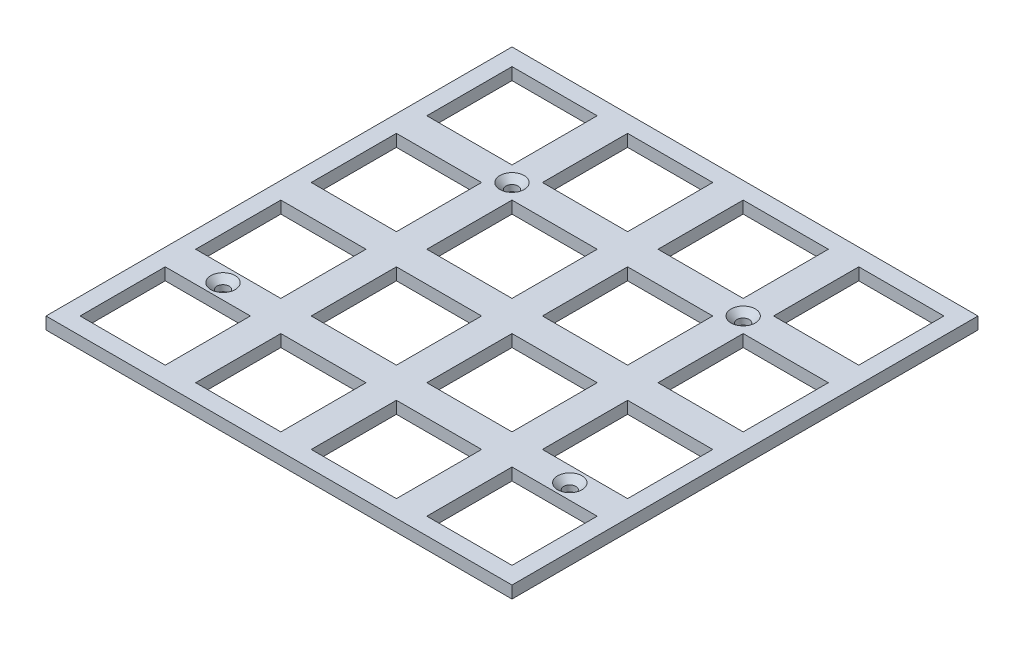
SolidWorks part; units mm, degrees
ref_plane "Front Plane" through (0, 0, 0) normal (0, 0, 1) x (1, 0, 0)
ref_plane "Top Plane" through (0, 0, 0) normal (0, 1, 0) x (1, 0, 0)
ref_plane "Right Plane" through (0, 0, 0) normal (1, 0, 0) x (0, 0, -1)
sketch "Sketch5" plane through (0, 0, 0) normal (1, 0, 0) x (0, 0, -1)
  line L0 (0, 0) -> (0, 13.4604) construction
sketch "Sketch1" plane through (0, 0, 0) normal (0, 1, 0) x (1, 0, 0)
  line L5 (-16.5, 21.5) -> (-16.5, 35.5)
  line L6 (-38.5, -38.5) -> (38.5, -38.5)
  line L11 (-38.5, -38.5) -> (-38.5, 38.5)
  line L12 (-38.5, 38.5) -> (38.5, 38.5)
  line L72 (38.5, -38.5) -> (38.5, 38.5)
  line L88 (-38.5, -38.5) -> (38.5, 38.5) construction
  line L89 (-38.5, 38.5) -> (38.5, -38.5) construction
  line L90 (-35.5, 21.5) -> (-21.5, 21.5)
  line L91 (-35.5, 21.5) -> (-35.5, 35.5)
  line L92 (-35.5, 35.5) -> (-21.5, 35.5)
  line L93 (-21.5, 21.5) -> (-21.5, 35.5)
  line L94 (-35.5, 21.5) -> (-21.5, 35.5) construction
  line L95 (-35.5, 35.5) -> (-21.5, 21.5) construction
  line L96 (-16.5, 21.5) -> (-2.5, 21.5)
  line L97 (-2.5, 21.5) -> (-2.5, 35.5)
  line L98 (-16.5, 35.5) -> (-2.5, 35.5)
  line L99 (2.5, 21.5) -> (2.5, 35.5)
  line L100 (2.5, 21.5) -> (16.5, 21.5)
  line L101 (16.5, 21.5) -> (16.5, 35.5)
  line L102 (2.5, 35.5) -> (16.5, 35.5)
  line L103 (21.5, 21.5) -> (21.5, 35.5)
  line L104 (21.5, 21.5) -> (35.5, 21.5)
  line L105 (35.5, 21.5) -> (35.5, 35.5)
  line L106 (21.5, 35.5) -> (35.5, 35.5)
  line L107 (-16.5, 2.5) -> (-16.5, 16.5)
  line L108 (-16.5, 2.5) -> (-2.5, 2.5)
  line L109 (-2.5, 2.5) -> (-2.5, 16.5)
  line L110 (-16.5, 16.5) -> (-2.5, 16.5)
  line L111 (2.5, 2.5) -> (2.5, 16.5)
  line L112 (2.5, 2.5) -> (16.5, 2.5)
  line L113 (16.5, 2.5) -> (16.5, 16.5)
  line L114 (2.5, 16.5) -> (16.5, 16.5)
  line L115 (21.5, 2.5) -> (21.5, 16.5)
  line L116 (21.5, 2.5) -> (35.5, 2.5)
  line L117 (35.5, 2.5) -> (35.5, 16.5)
  line L118 (21.5, 16.5) -> (35.5, 16.5)
  line L119 (-16.5, -16.5) -> (-16.5, -2.5)
  line L120 (-16.5, -16.5) -> (-2.5, -16.5)
  line L121 (-2.5, -16.5) -> (-2.5, -2.5)
  line L122 (-16.5, -2.5) -> (-2.5, -2.5)
  line L123 (2.5, -16.5) -> (2.5, -2.5)
  line L124 (2.5, -16.5) -> (16.5, -16.5)
  line L125 (16.5, -16.5) -> (16.5, -2.5)
  line L126 (2.5, -2.5) -> (16.5, -2.5)
  line L127 (21.5, -16.5) -> (21.5, -2.5)
  line L128 (21.5, -16.5) -> (35.5, -16.5)
  line L129 (35.5, -16.5) -> (35.5, -2.5)
  line L130 (21.5, -2.5) -> (35.5, -2.5)
  line L131 (-16.5, -35.5) -> (-16.5, -21.5)
  line L132 (-16.5, -35.5) -> (-2.5, -35.5)
  line L133 (-2.5, -35.5) -> (-2.5, -21.5)
  line L134 (-16.5, -21.5) -> (-2.5, -21.5)
  line L135 (2.5, -35.5) -> (2.5, -21.5)
  line L136 (2.5, -35.5) -> (16.5, -35.5)
  line L137 (16.5, -35.5) -> (16.5, -21.5)
  line L138 (2.5, -21.5) -> (16.5, -21.5)
  line L139 (21.5, -35.5) -> (21.5, -21.5)
  line L140 (21.5, -35.5) -> (35.5, -35.5)
  line L141 (35.5, -35.5) -> (35.5, -21.5)
  line L142 (21.5, -21.5) -> (35.5, -21.5)
  line L143 (-35.5, 2.5) -> (-35.5, 16.5)
  line L144 (-35.5, 2.5) -> (-21.5, 2.5)
  line L145 (-21.5, 2.5) -> (-21.5, 16.5)
  line L146 (-35.5, 16.5) -> (-21.5, 16.5)
  line L147 (-35.5, -16.5) -> (-35.5, -2.5)
  line L148 (-35.5, -16.5) -> (-21.5, -16.5)
  line L149 (-21.5, -16.5) -> (-21.5, -2.5)
  line L150 (-35.5, -2.5) -> (-21.5, -2.5)
  line L151 (-35.5, -35.5) -> (-35.5, -21.5)
  line L152 (-35.5, -35.5) -> (-21.5, -35.5)
  line L153 (-21.5, -35.5) -> (-21.5, -21.5)
  line L154 (-35.5, -21.5) -> (-21.5, -21.5)
  line L155 (-35.5, 21.5) -> (-16.5, 21.5) construction
  line L156 (-35.5, 21.5) -> (-35.5, 2.5) construction
  point P0 (0, 0)
  point P6 (-28.5, 28.5)
  dimension "D1" = 3
  dimension "D2" = 14
  dimension "D5" = 90
  dimension "D6" = 19
  dimension "D7" = 19
  dimension "D3" = 4
  dimension "D8" = 77
  dimension "D9" = 5
  dimension "D4" = 4
extrude "Boss-Extrude1" add sketch "Sketch1" along normal blind 2
sketch "Sketch2" plane through (0, 2, 0) normal (0, 1, 0) x (1, 0, 0)
  line L0 (-28.5, -16.5) -> (-28.5, -21.5) construction
  line L5 (-35.5, -16.5) -> (-21.5, -16.5) construction
  line L7 (-21.5, -21.5) -> (-35.5, -21.5) construction
  line L8 (-28.5, -19) -> (0, -19) construction
  line L9 (-21.5, 16.5) -> (-16.5, 16.5) construction
  line L10 (-21.5, 16.5) -> (-21.5, 21.5) construction
  line L11 (-21.5, 21.5) -> (-16.5, 21.5) construction
  line L12 (-16.5, 16.5) -> (-16.5, 21.5) construction
  line L15 (-21.5, 16.5) -> (-16.5, 21.5) construction
  line L20 (-21.5, 21.5) -> (-16.5, 16.5) construction
  line L22 (-19, 19) -> (0, 19) construction
  circle A0 centre (-19, 19) radius 1
  circle A1 centre (-28.5, -19) radius 1
  point P8 (-19, 19)
  point P17 (-28.5, -19)
  dimension "D1" = 2
  dimension "D2" = 2
  dimension "D3" = 19
  dimension "D4" = 28.5
extrude "Cut-Extrude1" cut sketch "Sketch2" against normal up to surface (2 mm away) up to face at (0, 0, 0)
sketch "Sketch3" plane through (0, 2, 0) normal (0, 1, 0) x (1, 0, 0)
  circle A2 centre (-19, 19) radius 2
  circle A3 centre (-19, 19) radius 2
  circle A4 centre (-28.5, -19) radius 2
  circle A5 centre (-28.5, -19) radius 2
  dimension "D1" = 1
  dimension "D2" = 1
extrude "Cut-Extrude2" [suppressed] cut sketch "Sketch3" against normal blind 1
chamfer "Chamfer1" distance 1 angle 45 2 edges at (-19, 2, -18) (-28.5, 2, 20)
mirror "Mirror1" about plane through (0, 0, 0) normal (1, 0, 0) of "Chamfer1", "Cut-Extrude1"
other "Move Face1" flip direction yes face at (38.5, 1, 0) face at (0, 1, -38.5) face at (0, 1, 38.5) face at (-38.5, 1, 0) offset 0.2 parameters "D1"=0.2
equation "\"screwhole\"=2"
equation "\"D2@Sketch2\"=\"screwhole\""
equation "\"D1@Sketch2\"=\"screwhole\""
